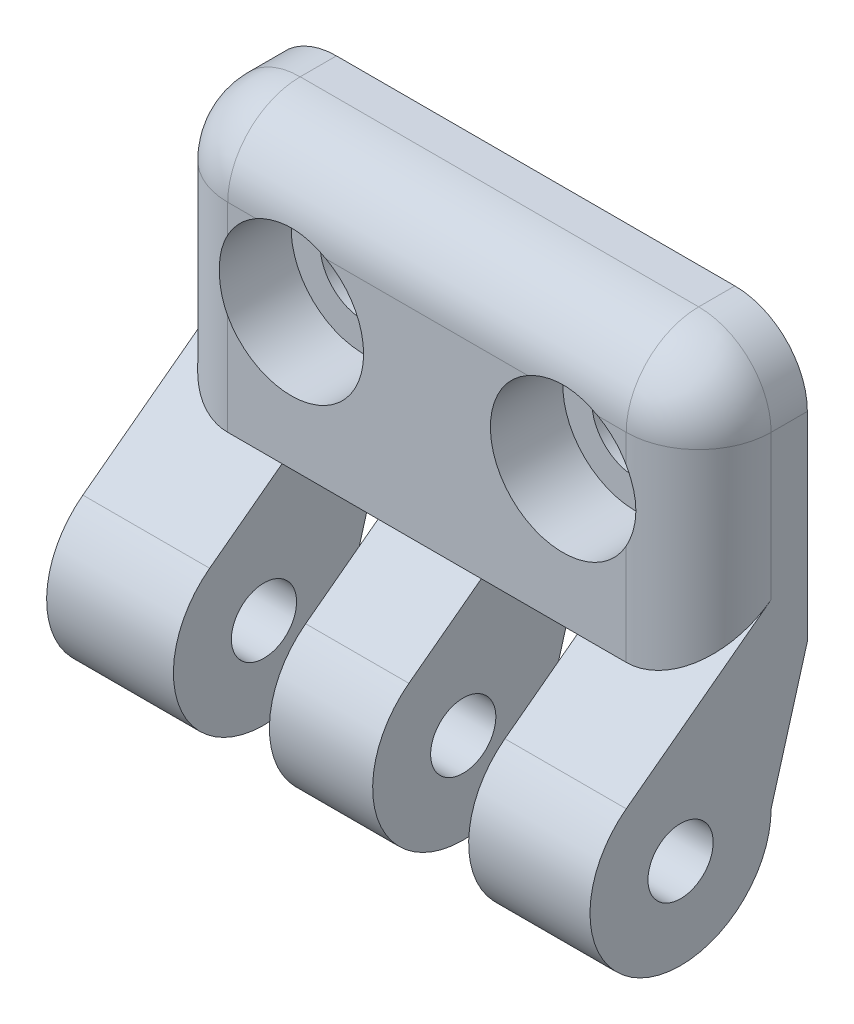
SolidWorks part; units mm, degrees
ref_plane "Front Plane" through (0, 0, 0) normal (0, 0, 1) x (1, 0, 0)
ref_plane "Top Plane" through (0, 0, 0) normal (0, 1, 0) x (1, 0, 0)
ref_plane "Right Plane" through (0, 0, 0) normal (1, 0, 0) x (0, 0, -1)
sketch "Sketch2" plane through (0, 0, 0) normal (0, 0, 1) x (1, 0, 0)
  line L1 (0, 0) -> (30, 0)
  line L2 (0, 0) -> (0, 15)
  line L3 (0, 15) -> (30, 15)
  line L4 (30, 0) -> (30, 15)
  dimension "D1" = 15
  dimension "D2" = 30
extrude "Boss-Extrude1" add sketch "Sketch2" along normal blind 6
hole_wizard "CBORE for M4 SHCS1" positions "Sketch3" profile "Sketch4" counterbore size "M4" standard "ANSI Metric" end condition through all
sketch "Sketch3" plane through (0, 0, 6) normal (0, 0, 1) x (1, 0, 0)
  line L0 (0, 15) -> (0, 0) construction
  line L1 (0, 0) -> (30, 0) construction
  point P0 (7.5, 7.5)
  point P2 (22.5, 7.5)
  dimension "D1" = 15
  dimension "D2" = 7.5
  dimension "D3" = 7.5
sketch "Sketch4" plane through (7.5, 7.5, 6) normal (1, 0, 0) x (0, -1, 0)
  line L0 (0, 0) -> (0, 6)
  line L1 (0, 6) -> (2.4, 6)
  line L3 (2.4, 6) -> (2.4, 4)
  line L4 (2.4, 4) -> (4, 4)
  line L5 (4, 4) -> (4, 0)
  line L7 (4, 0) -> (0, 0)
  line L11 (0, -6.35) -> (0, 107.95) construction
  dimension "Thru Hole Dia." = 4.8
  dimension "Thru Hole Depth" = 6
  dimension "C'Bore Dia." = 8
  dimension "C'Bore Depth" = 4
sketch "Sketch5" plane through (30, 0, 0) normal (1, 0, 0) x (0, 0, -1)
  line L0 (0, 0) -> (0, 15) construction
  line L1 (-6, 0) -> (0, 0) construction
  line L2 (0, 0) -> (-2, -7)
  line L3 (0, 0) -> (-6, 0)
  line L4 (-6, 0) -> (-10, -3)
  arc A0 (-10, -3) -> (-2, -7) centre (-7, -7) ccw
  dimension "D3" = 10
  dimension "D1" = 7
  dimension "D2" = 7
extrude "Boss-Extrude2" add sketch "Sketch5" against normal up to surface (30 mm away) up to face at (0, 7.5, 3)
sketch "Sketch6" plane through (0, 15, 0) normal (0, 1, 0) x (1, 0, 0)
  line L18 (23.3, -16.1356) -> (18, -16.1356)
  line L19 (23.3, -16.1356) -> (23.3, 4.2995)
  line L20 (23.3, 4.2995) -> (18, 4.2995)
  line L21 (18, -16.1356) -> (18, 4.2995)
  line L22 (12.3, -13.7315) -> (7, -13.7315)
  line L23 (12.3, -13.7315) -> (12.3, 3.316)
  line L24 (12.3, 3.316) -> (7, 3.316)
  line L25 (7, -13.7315) -> (7, 3.316)
  dimension "D1" = 5.3
  dimension "D2" = 5.3
  dimension "D3" = 5.7
extrude "Cut-Extrude1" cut sketch "Sketch6" against normal through all from vertex starting at point (30, 0, 6)
fillet "Fillet1" radius 4 5 edges at (0, 7.5, 6) (0, 15, 3) (30, 15, 3) (30, 7.5, 6) (15, 15, 6)
hole_wizard "CBORE for M3 SHCS1" positions "Sketch7" profile "Sketch8" counterbore size "M3" standard "ANSI Metric" end condition through all
sketch "Sketch7" plane through (0, 0, 0) normal (-1, 0, 0) x (0, 0, 1)
  arc A0 (2, -7) -> (10, -3) centre (7, -7) ccw construction
  point P0 (7, -7)
  dimension "D1" = 0
sketch "Sketch8" plane through (0, -7, 7) normal (0, 1, 0) x (0, 0, 1)
  line L0 (0, 0) -> (0, 30)
  line L1 (0, 30) -> (1.8, 30)
  line L3 (1.8, 30) -> (1.8, 3)
  line L4 (1.8, 3) -> (3.25, 3)
  line L5 (3.25, 3) -> (3.25, 0)
  line L7 (3.25, 0) -> (0, 0)
  line L11 (0, -6.35) -> (0, 107.95) construction
  dimension "Thru Hole Dia." = 3.6
  dimension "Thru Hole Depth" = 30
  dimension "C'Bore Dia." = 6.5
  dimension "C'Bore Depth" = 3
